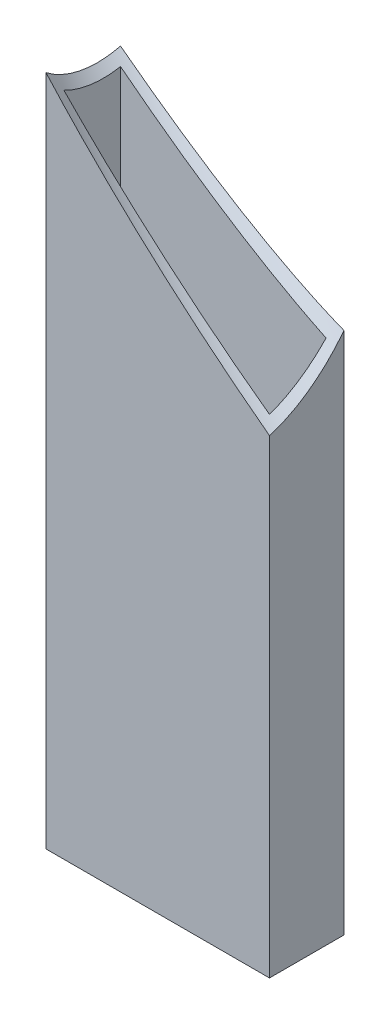
SolidWorks part; units mm, degrees
note: '?' marks a value the reader was unsure of.
material "A500"
ref_plane "Front Plane" through (0, 0, 0) normal (0, 0, 1) x (1, 0, 0)
ref_plane "Top Plane" through (0, 0, 0) normal (0, 1, 0) x (1, 0, 0)
ref_plane "Right Plane" through (0, 0, 0) normal (1, 0, 0) x (0, 0, -1)
sketch "Sketch1" plane through (0, 0, 0) normal (0, 1, 0) x (1, 0, 0)
  line L0 (0, 9.652) -> (0, 12.7) construction
  line L1 (-38.1, 12.7) -> (38.1, 12.7)
  line L2 (-38.1, 12.7) -> (-38.1, -12.7)
  line L3 (-38.1, -12.7) -> (38.1, -12.7)
  line L4 (38.1, 12.7) -> (38.1, -12.7)
  line L5 (-35.052, 9.652) -> (35.052, 9.652)
  line L6 (-35.052, 9.652) -> (-35.052, -9.652)
  line L7 (-35.052, -9.652) -> (35.052, -9.652)
  line L8 (35.052, 9.652) -> (35.052, -9.652)
  line L9 (35.052, 0) -> (38.1, 0) construction
  line L10 (0, -9.652) -> (0, -12.7) construction
  line L11 (-35.052, 0) -> (-38.1, 0) construction
  line L12 (0, 9.652) -> (0, 0) construction
  line L13 (0, 0) -> (-35.052, 0) construction
  dimension "D1" = 76.2
  dimension "D2" = 25.4
  dimension "D3" = 3.048
extrude "Boss-Extrude1" add sketch "Sketch1" along normal up to vertex (241.0919 mm away)
ref_plane "Plane1" through (0, 0, 0) normal (0, 0, 1) x (1, 0, 0)
sketch "Sketch2" plane through (0, 0, 0) normal (0, 0, 1) x (1, 0, 0)
  line L0 (0, 0) -> (0, 241.0919) construction
  line L1 (-38.1, 241.0919) -> (38.1, 241.0919) construction
  line L2 (0, 120.546) -> (-38.1, 120.546) construction
  line L3 (-38.1, 241.0919) -> (-38.1, 0) construction
  line L4 (0, 120.546) -> (38.1, 120.546) construction
  line L5 (38.1, 241.0919) -> (38.1, 0) construction
ref_axis "Axis1" through (0, 241.0919, 0) along (0, -1, 0)?
sketch "Sketch3" plane through (0, 241.0919, 0) normal (0, 1, 0) x (1, 0, 0)
  line L0 (35.052, -9.652) -> (35.052, 9.652) construction
  line L1 (-35.052, -9.652) -> (35.052, -9.652) construction
  line L2 (-35.052, 9.652) -> (-35.052, -9.652) construction
  line L3 (35.052, 9.652) -> (-35.052, 9.652) construction
  line L4 (-38.1, 12.7) -> (-38.1, -12.7)
  line L5 (-38.1, -12.7) -> (38.1, -12.7)
  line L6 (38.1, -12.7) -> (38.1, 12.7)
  line L7 (38.1, 12.7) -> (-38.1, 12.7)
  line L8 (-38.1, 12.7) -> (-38.1, -12.7)
  line L9 (-38.1, -12.7) -> (38.1, -12.7)
  line L10 (38.1, -12.7) -> (38.1, 12.7)
  line L11 (38.1, 12.7) -> (-38.1, 12.7)
  line L12 (35.052, -9.652) -> (35.052, 9.652)
  line L13 (-35.052, -9.652) -> (35.052, -9.652)
  line L14 (-35.052, 9.652) -> (-35.052, -9.652)
  line L15 (35.052, 9.652) -> (-35.052, 9.652)
  dimension "D1" = 0
extrude "Boss-Extrude2" add sketch "Sketch3" along normal blind 3.048
sketch "Sketch4" plane through (0, 0, 0) normal (0, -1, 0) x (1, 0, 0)
  line L0 (35.052, 9.652) -> (35.052, -9.652) construction
  line L1 (-35.052, 9.652) -> (35.052, 9.652) construction
  line L2 (35.052, -9.652) -> (-35.052, -9.652) construction
  line L3 (-35.052, -9.652) -> (-35.052, 9.652) construction
  line L4 (-38.1, 12.7) -> (-38.1, -12.7)
  line L5 (-38.1, -12.7) -> (38.1, -12.7)
  line L6 (38.1, -12.7) -> (38.1, 12.7)
  line L7 (38.1, 12.7) -> (-38.1, 12.7)
  line L8 (-38.1, 12.7) -> (-38.1, -12.7)
  line L9 (-38.1, -12.7) -> (38.1, -12.7)
  line L10 (38.1, -12.7) -> (38.1, 12.7)
  line L11 (38.1, 12.7) -> (-38.1, 12.7)
  line L12 (35.052, 9.652) -> (35.052, -9.652)
  line L13 (-35.052, 9.652) -> (35.052, 9.652)
  line L14 (35.052, -9.652) -> (-35.052, -9.652)
  line L15 (-35.052, -9.652) -> (-35.052, 9.652)
  dimension "D1" = 0
extrude "Boss-Extrude3" [suppressed] add sketch "Sketch4" along normal blind 38.1
ref_plane "Plane2" through (0, 0, 0) normal (-0.2509, 0.7737, -0.5818) x (0.968, 0.2045, -0.1455)
ref_plane "Plane3" through (-101.4436, 327.1509, -35.7608) normal (0.7364, -0.6247, 0.2596) x (0.2755, -0.0735, -0.9585)
sketch "Sketch5" plane through (-101.4436, 327.1509, -35.7608) normal (0.7364, -0.6247, 0.2596) x (0.2755, -0.0735, -0.9585)
  circle A0 centre (0, 0) radius 38.1 construction
  circle A1 centre (0, 0) radius 38.1
extrude "Cut-Extrude2" cut sketch "Sketch5" along normal up to vertex
equation "\"tubeMainWidth\"= 76.2mm"
equation "\"tubeSecondWidth\"= 25.4mm"
equation "\"tubeThickness\"= 3.048mm"
equation "\"halfMainWidthOfTubing\"= (\"tubeMainWidth\"/2)"
equation "\"D1@Sketch1\"=\"tubeMainWidth\""
equation "\"D2@Sketch1\"=\"tubeSecondWidth\""
equation "\"D3@Sketch1\"=\"tubeThickness\""
equation "\"D1@Boss-Extrude2\"=\"tubeThickness\""
equation "\"D1@Boss-Extrude3\"=\"halfMainWidthOfTubing\""
